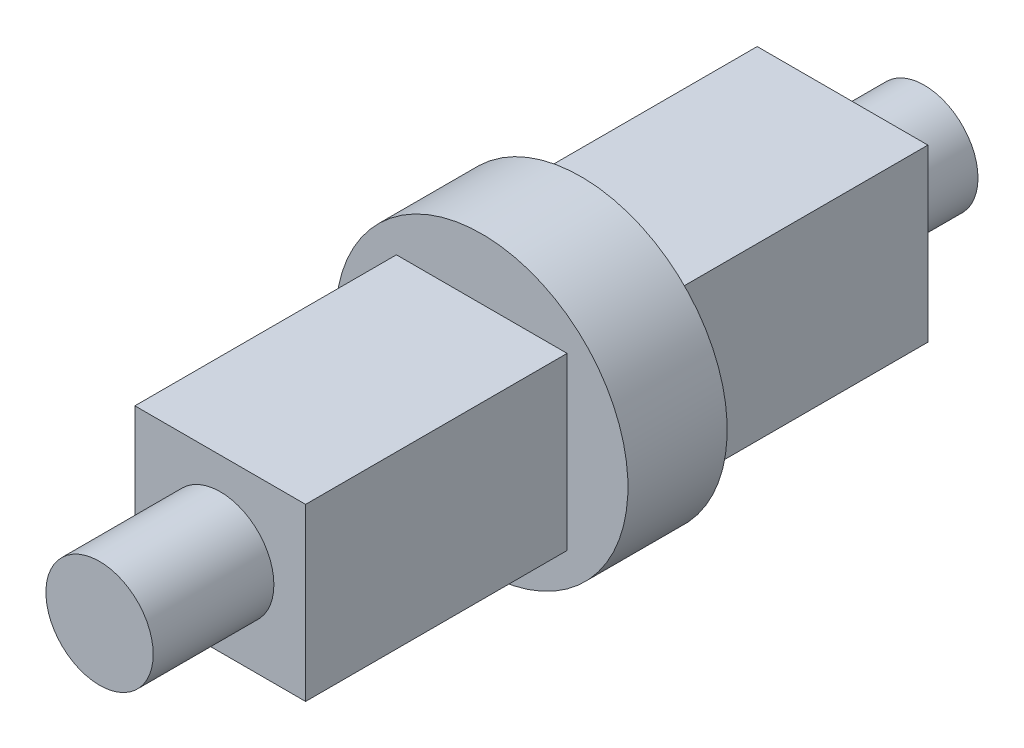
SolidWorks part; units mm, degrees
ref_plane "Ebene vorne" through (0, 0, 0) normal (0, 0, 1) x (1, 0, 0)
ref_plane "Ebene oben" through (0, 0, 0) normal (0, 1, 0) x (1, 0, 0)
ref_plane "Ebene rechts" through (0, 0, 0) normal (1, 0, 0) x (0, 0, -1)
sketch "Skizze1" plane through (0, 0, 0) normal (0, 0, 1) x (1, 0, 0)
  circle A0 centre (0, 0) radius 4
  dimension "D1" = 8
extrude "Aufsatz-Linear austragen1" add sketch "Skizze1" along normal blind 61.5
sketch "Skizze2" plane through (0, 0, 61.5) normal (0, 0, 1) x (1, 0, 0)
  circle A0 centre (0, 0) radius 5
sketch "Skizze3" plane through (0, 0, 0) normal (0, 0, -1) x (-1, 0, 0)
  circle A0 centre (0, 0) radius 2.25
  dimension "D1" = 4.5
extrude "Schnitt-Linear austragen1" cut sketch "Skizze3" against normal blind 18
thread "Gewinde1" pitch 0.8 method cut profile "Gewindeprofil1" start angle 0, offset 0, length 16, pitch 0.8, diameter 4.5
ref_plane "Ebene1" through (2.25, 0, 0) normal (0, -1, 0) x (1, 0, 0)
sketch "Gewindeprofil1" plane through (2.25, 0, 0) normal (0, -1, 0) x (1, 0, 0)
  line L0 (0, 0) -> (0, 0.8) construction
  line L1 (0, 0) -> (0.433, 0.25)
  line L2 (0.433, 0.25) -> (0.433, 0.35)
  line L3 (0.433, 0.35) -> (0, 0.6)
  line L4 (0.433, 0.3) -> (0, 0.3) construction
  line L11 (0, 0) -> (0, 0.6)
  point P2 (0, 0)
  dimension "Pitch" = 0.8
  dimension "Profile_Angle" = 60
  dimension "Profile_Land" = 0.1
  dimension "Profile_Height" = 0.433
ref_plane "Ebene2" through (0, 0, 52.5) normal (0, 0, 1) x (1, 0, 0)
sketch "Skizze4" plane through (0, 0, 52.5) normal (0, 0, 1) x (1, 0, 0)
  circle A0 centre (0, 0) radius 9
sketch "Skizze6" plane through (0, 0, 52.5) normal (0, 0, 1) x (1, 0, 0)
  line L1 (-6.364, 6.364) -> (6.364, 6.364)
  line L2 (-6.364, 6.364) -> (-6.364, -6.364)
  line L3 (-6.364, -6.364) -> (6.364, -6.364)
  line L4 (6.364, 6.364) -> (6.364, -6.364)
  line L5 (-6.364, 6.364) -> (6.364, -6.364) construction
  line L6 (-6.364, -6.364) -> (6.364, 6.364) construction
  circle A0 centre (0, 0) radius 9 construction
  point P0 (0, 0)
extrude "Aufsatz-Linear austragen2" add sketch "Skizze6" against normal blind 19.5
ref_plane "Ebene3" through (0, 0, 25.6) normal (0, 0, 1) x (1, 0, 0)
sketch "Skizze7" plane through (0, 0, 25.6) normal (0, 0, 1) x (1, 0, 0)
  circle A0 centre (0, 0) radius 9
sketch "Skizze8" plane through (0, 0, 25.6) normal (0, 0, 1) x (1, 0, 0)
  line L1 (-6.364, 6.364) -> (6.364, 6.364)
  line L2 (-6.364, 6.364) -> (-6.364, -6.364)
  line L3 (-6.364, -6.364) -> (6.364, -6.364)
  line L4 (6.364, 6.364) -> (6.364, -6.364)
  line L5 (-6.364, 6.364) -> (6.364, -6.364) construction
  line L6 (-6.364, -6.364) -> (6.364, 6.364) construction
  circle A0 centre (0, 0) radius 9 construction
  point P0 (0, 0)
extrude "Aufsatz-Linear austragen3" add sketch "Skizze8" against normal blind 19.5
sketch "Skizze9" plane through (0, 0, 33) normal (0, 0, -1) x (-1, 0, 0)
  circle A0 centre (0, 0) radius 10.9
  dimension "D1" = 21.8
extrude "Aufsatz-Linear austragen4" add sketch "Skizze9" along normal blind 7.4
